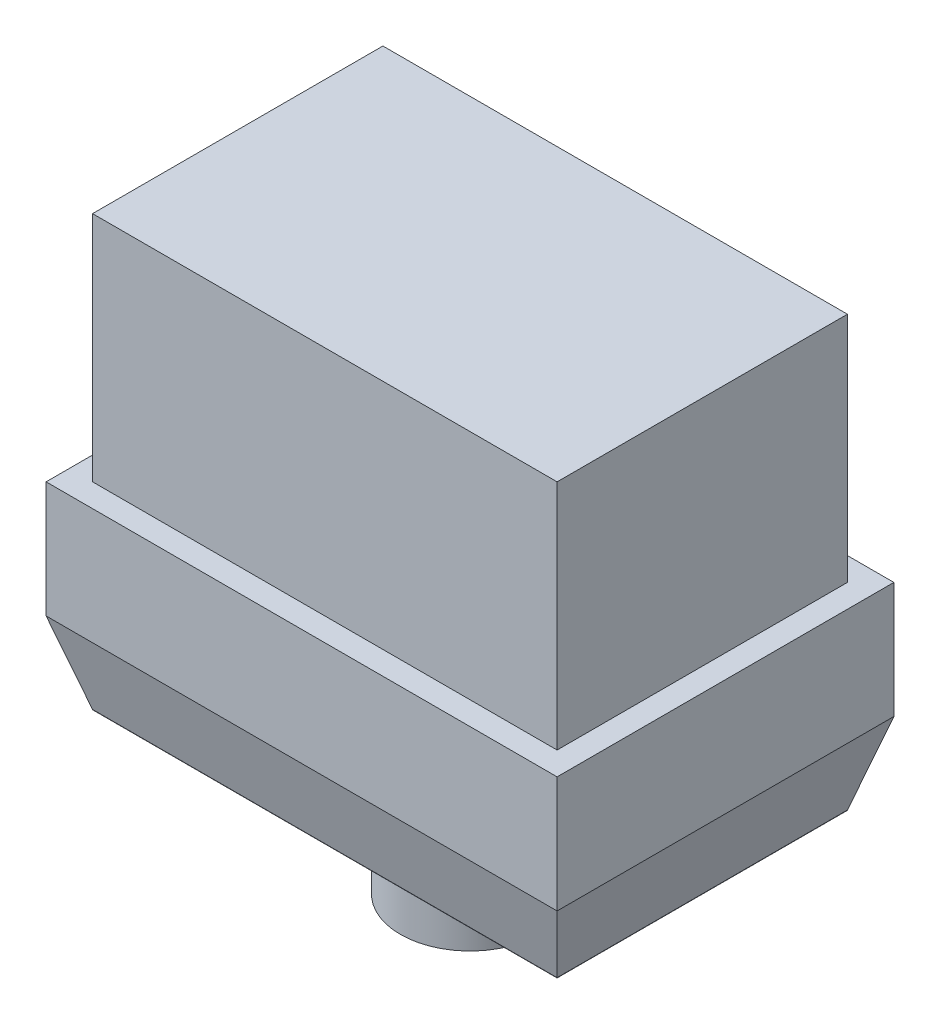
SolidWorks part; units mm, degrees
ref_plane "Front Plane" through (0, 0, 0) normal (0, 0, 1) x (1, 0, 0)
ref_plane "Top Plane" through (0, 0, 0) normal (0, 1, 0) x (1, 0, 0)
ref_plane "Right Plane" through (0, 0, 0) normal (1, 0, 0) x (0, 0, -1)
sketch "Sketch1" plane through (0, 0, 0) normal (0, 1, 0) x (1, 0, 0)
  line L1 (0, 0) -> (40, 0)
  line L2 (0, 0) -> (0, 25)
  line L3 (0, 25) -> (40, 25)
  line L4 (40, 0) -> (40, 25)
  dimension "D1" = 40
  dimension "D2" = 25
extrude "Boss-Extrude1" add sketch "Sketch1" along normal blind 30
sketch "Sketch2" plane through (0, 0, 0) normal (0, 1, 0) x (1, 0, 0)
  line L0 (40, 25) -> (0, 25) construction
  line L1 (-2, -2) -> (42, -2)
  line L2 (-2, -2) -> (-2, 27)
  line L3 (-2, 27) -> (42, 27)
  line L4 (42, -2) -> (42, 27)
  line L6 (0, 25) -> (0, 27) construction
  line L7 (40, 25) -> (42, 25) construction
  line L8 (40, 0) -> (40, -2) construction
  line L9 (0, 25) -> (-2, 25) construction
  dimension "D1" = 2
extrude "Boss-Extrude2" add sketch "Sketch2" along normal blind 10
sketch "Sketch3" plane through (0, 0, 0) normal (0, -1, 0) x (1, 0, 0)
  line L5 (0, -25) -> (40, -25)
  line L6 (0, -25) -> (0, 0)
  line L7 (0, 0) -> (40, 0)
  line L8 (40, -25) -> (40, 0)
extrude "Boss-Extrude3" add sketch "Sketch3" along normal blind 14
sketch "Sketch4" plane through (0, -14, 0) normal (0, -1, 0) x (1, 0, 0)
  line L1 (0, -25) -> (40, -25)
  line L2 (0, -25) -> (0, 0)
  line L3 (0, 0) -> (40, 0)
  line L4 (40, -25) -> (40, 0)
extrude "Cut-Extrude1" cut sketch "Sketch4" against normal blind 7
sketch "Sketch5" plane through (0, -7, 0) normal (0, -1, 0) x (1, 0, 0)
  line L0 (20, 0) -> (20, -25) construction
  line L1 (40, 0) -> (0, 0) construction
  line L2 (0, -12.5) -> (40, -12.5) construction
  line L3 (0, 0) -> (0, -25) construction
  line L4 (40, -25) -> (40, 0) construction
  line L5 (0, -25) -> (40, -25) construction
  circle A0 centre (6.5, -12.5) radius 2.65
  circle A1 centre (6.5, -12.5) radius 4
  circle A2 centre (33.5, -12.5) radius 4
  circle A3 centre (33.5, -12.5) radius 2.65
  dimension "D1" = 5.3
  dimension "D2" = 8
  dimension "D3" = 6.5
extrude "Cut-Extrude2" cut sketch "Sketch5" against normal blind 3
sketch "Sketch6" plane through (0, -7, 0) normal (0, -1, 0) x (1, 0, 0)
  line L0 (0, 0) -> (40, -25) construction
  line L1 (40, 0) -> (0, -25) construction
  circle A0 centre (20, -12.5) radius 6
extrude "Boss-Extrude4" add sketch "Sketch6" along normal blind 10
chamfer "Chamfer1" distance 2 angle 74 4 edges at (40, 0, -12.5) (20, 0, -25) (0, 0, -12.5) (20, 0, 0) first distance on face at (20, 0, -12.5)
